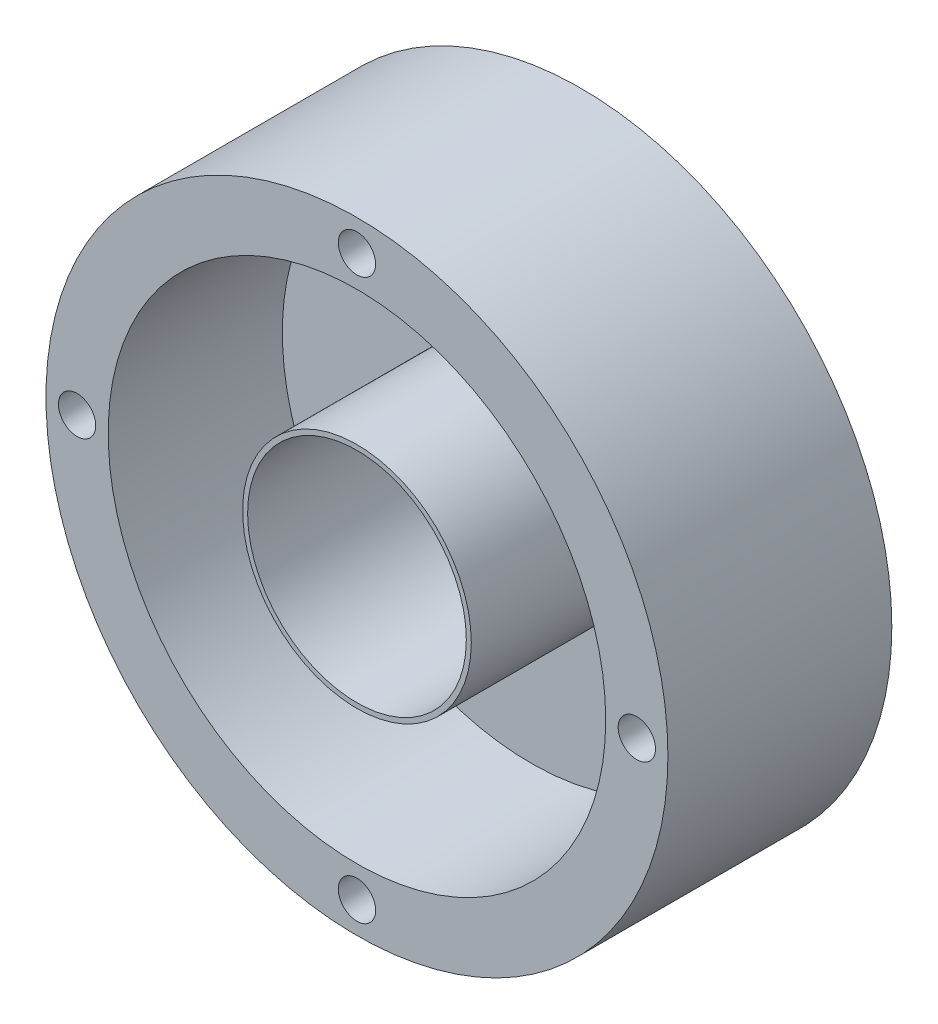
SolidWorks part; units mm, degrees
ref_plane "Front Plane" through (0, 0, 0) normal (0, 0, 1) x (1, 0, 0)
ref_plane "Top Plane" through (0, 0, 0) normal (0, 1, 0) x (1, 0, 0)
ref_plane "Right Plane" through (0, 0, 0) normal (1, 0, 0) x (0, 0, -1)
sketch "Sketch1" plane through (0, 0, 0) normal (0, 0, 1) x (1, 0, 0)
  circle A0 centre (0, 0) radius 25
  dimension "D1" = 50
extrude "Boss-Extrude1" add sketch "Sketch1" along normal blind 18
sketch "Sketch2" plane through (0, 0, 18) normal (0, 0, 1) x (1, 0, 0)
  circle A0 centre (0, 0) radius 20
  dimension "D1" = 40
extrude "Cut-Extrude1" cut sketch "Sketch2" against normal blind 14
sketch "Sketch3" plane through (0, 0, 0) normal (0, 0, -1) x (-1, 0, 0)
  line L1 (-10, -5) -> (10, -5)
  line L2 (-10, -5) -> (-10, 5)
  line L3 (-10, 5) -> (10, 5)
  line L4 (10, -5) -> (10, 5)
  line L5 (-10, -5) -> (10, 5) construction
  line L6 (-10, 5) -> (10, -5) construction
  point P0 (0, 0)
  dimension "D1" = 10
  dimension "D2" = 20
extrude "Boss-Extrude2" add sketch "Sketch3" along normal blind 8
fillet "Fillet2" radius 10 2 edges at (-10, 0, 0) (10, 0, 0)
fillet "Fillet3" radius 10 2 edges at (10, 0, -8) (-10, 0, -8)
fillet "Fillet4" radius 2 2 edges at (0, 5, 0) (0, -5, 0)
sketch "Sketch4" plane through (0, -5, 0) normal (0, -1, 0) x (1, 0, 0)
  line L1 (-5, 0) -> (5, 0)
  line L2 (-5, 0) -> (-5, -3.25)
  line L3 (-5, -3.25) -> (5, -3.25)
  line L4 (5, 0) -> (5, -3.25)
  dimension "D1" = 10
  dimension "D2" = 5
  dimension "D3" = 3.25
extrude "Cut-Extrude2" cut sketch "Sketch4" against normal through all both and the other way through all
sketch "Sketch5" plane through (0, 0, 18) normal (0, 0, 1) x (1, 0, 0)
  circle A0 centre (0, 22.5) radius 1.5
  circle A1 centre (22.5, 0) radius 1.5
  circle A2 centre (0, -22.5) radius 1.5
  circle A3 centre (-22.5, 0) radius 1.5
  point P12 (0, 0)
  dimension "D1" = 3
  dimension "D2" = 22.5
  dimension "D3" = 4
extrude "Cut-Extrude3" cut sketch "Sketch5" against normal through all both
sketch "Sketch6" plane through (0, 0, 18) normal (0, 0, 1) x (1, 0, 0)
  circle A0 centre (0, 0) radius 8.7915
  circle A1 centre (0, 0) radius 9.1915
  dimension "D1" = 0.4
extrude "Boss-Extrude3" add sketch "Sketch6" against normal blind 13.4 separate body
